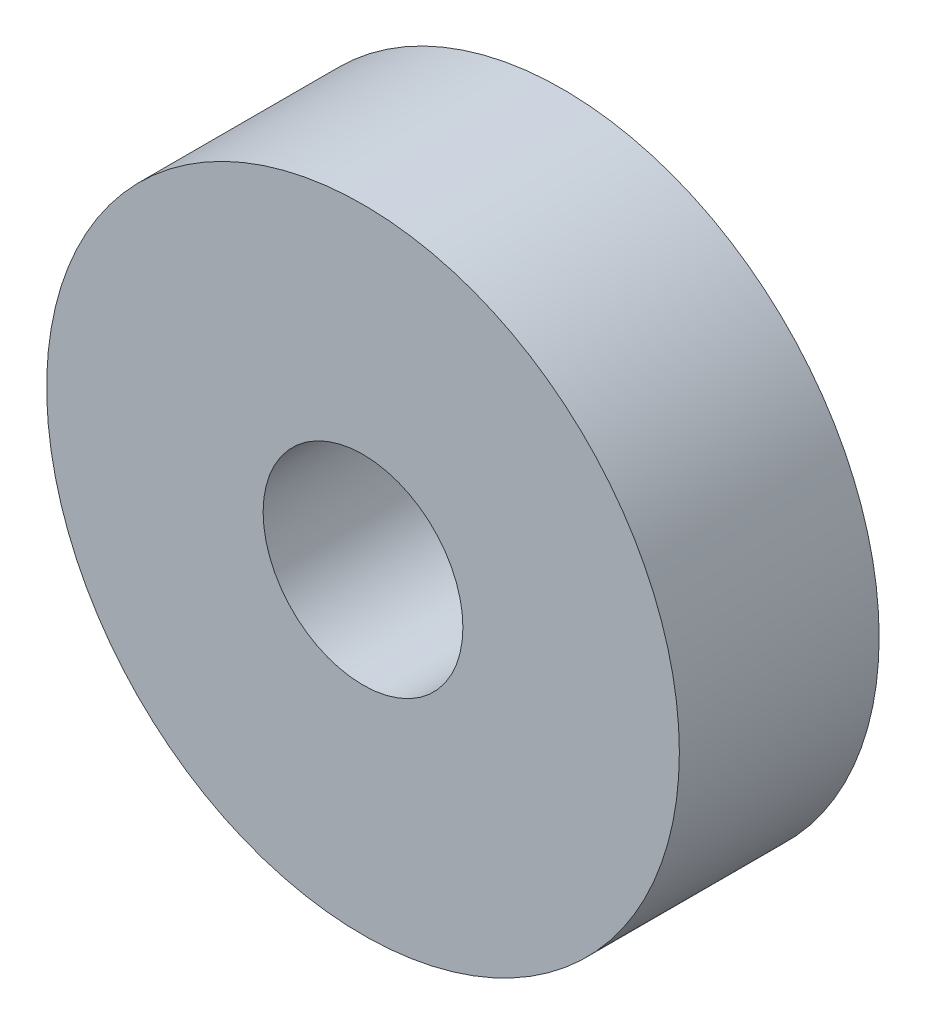
SolidWorks part; units mm, degrees
ref_plane "Front Plane" through (0, 0, 0) normal (0, 0, 1) x (1, 0, 0)
ref_plane "Top Plane" through (0, 0, 0) normal (0, 1, 0) x (1, 0, 0)
ref_plane "Right Plane" through (0, 0, 0) normal (1, 0, 0) x (0, 0, -1)
sketch "Sketch1" plane through (0, 0, 0) normal (0, 0, 1) x (1, 0, 0)
  circle A0 centre (0, 0) radius 9.5
  circle A1 centre (0, 0) radius 3
  dimension "D1" = 19
  dimension "D2" = 6
extrude "Boss-Extrude1" add sketch "Sketch1" along normal mid plane 6
